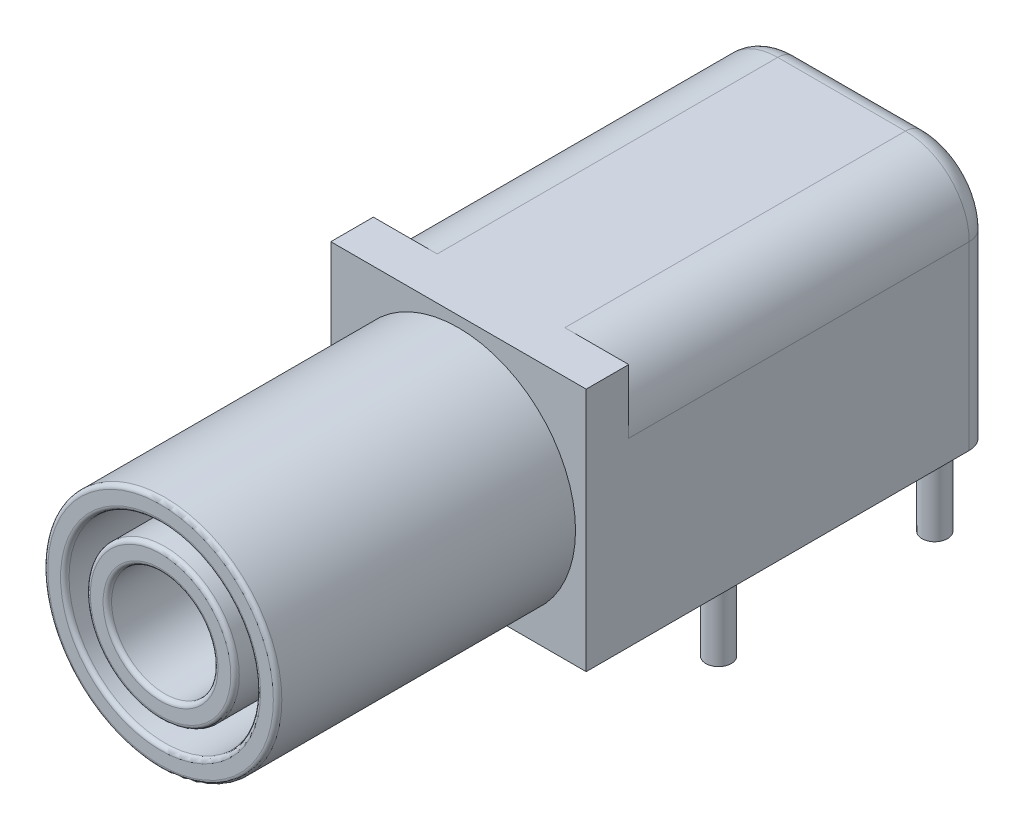
SolidWorks part; units mm, degrees
ref_plane "Front Plane" through (0, 0, 0) normal (0, 0, 1) x (1, 0, 0)
ref_plane "Top Plane" through (0, 0, 0) normal (0, 1, 0) x (1, 0, 0)
ref_plane "Right Plane" through (0, 0, 0) normal (1, 0, 0) x (0, 0, -1)
sketch "Sketch1" plane through (0, 0, 0) normal (0, 0, 1) x (1, 0, 0)
  line L1 (-6, -5.5) -> (6, -5.5)
  line L2 (-6, -5.5) -> (-6, 6)
  line L3 (-6, 6) -> (6, 6)
  line L4 (6, -5.5) -> (6, 6)
  circle A0 centre (0, 0) radius 5.5
  circle A1 centre (0, 0) radius 2.5
  circle A2 centre (0, 0) radius 4.5
  circle A3 centre (0, 0) radius 3.5
  dimension "D1" = 6
extrude "Boss-Extrude1" add sketch "Sketch1" along normal blind 14 contours A0 A2 | A3 A1 region at (-3.7791, 3.7791, 0) region at (-3.401, 0, 0)
extrude "Boss-Extrude2" add sketch "Sketch1<3>" against normal blind 19 contours L3 L4 L1 L2
sketch "Sketch1<3>" plane through (0, 0, 0) normal (0, 0, 1) x (1, 0, 0) same geometry as "Sketch1"
fillet "Fillet1" radius 0.2 4 edges at (2.5, 0, 14) (3.5, 0, 14) (4.5, 0, 14) (5.5, 0, 14)
sketch "Sketch2" plane through (0, 0, -19) normal (0, 0, -1) x (-1, 0, 0)
  line L0 (-8.7474, 11) -> (-8.7474, 1)
  line L1 (-8.7474, 1) -> (-6, 1)
  line L2 (-6, -5.5) -> (-6, 6) construction
  line L3 (-6, 1) -> (-6, 3)
  line L4 (-3, 6) -> (3, 6)
  line L5 (6, 3) -> (6, 1)
  line L6 (6, -5.5) -> (6, 6) construction
  line L7 (6, 1) -> (7.9839, 1)
  line L8 (7.9839, 1) -> (7.9839, 11)
  line L9 (7.9839, 11) -> (-8.7474, 11)
  arc A0 (6, 3) -> (3, 6) centre (3, 3) ccw
  arc A1 (-3, 6) -> (-6, 3) centre (-3, 3) ccw
  point P16 (6, 6)
  point P19 (-6, 6)
  dimension "D3" = 3
  dimension "D1" = 5
  dimension "D2" = 5
extrude "Cut-Extrude1" cut sketch "Sketch2" against normal blind 17
fillet "Fillet3" radius 1 5 edges at (-6, -1.25, -19) (-5.1213, 5.1213, -19) (0, 6, -19) (5.1213, 5.1213, -19) (6, -1.25, -19)
sketch "Sketch3" plane through (0, -5.5, 0) normal (0, -1, 0) x (1, 0, 0)
  line L0 (0, 0) -> (0, -19) construction
  line L1 (-5, -19) -> (5, -19) construction
  circle A0 centre (0, -13.5) radius 1.1
  circle A1 centre (5.08, -17.3) radius 0.6
  circle A2 centre (-5.08, -7.14) radius 0.6
  circle A3 centre (-5.08, -17.3) radius 0.6
  circle A4 centre (5.08, -7.14) radius 0.6
  dimension "D1" = 13.5
  dimension "D2" = 3.8
  dimension "D3" = 10.16
  dimension "D4" = 5.08
extrude "Boss-Extrude3" add sketch "Sketch3" along normal blind 3.4
